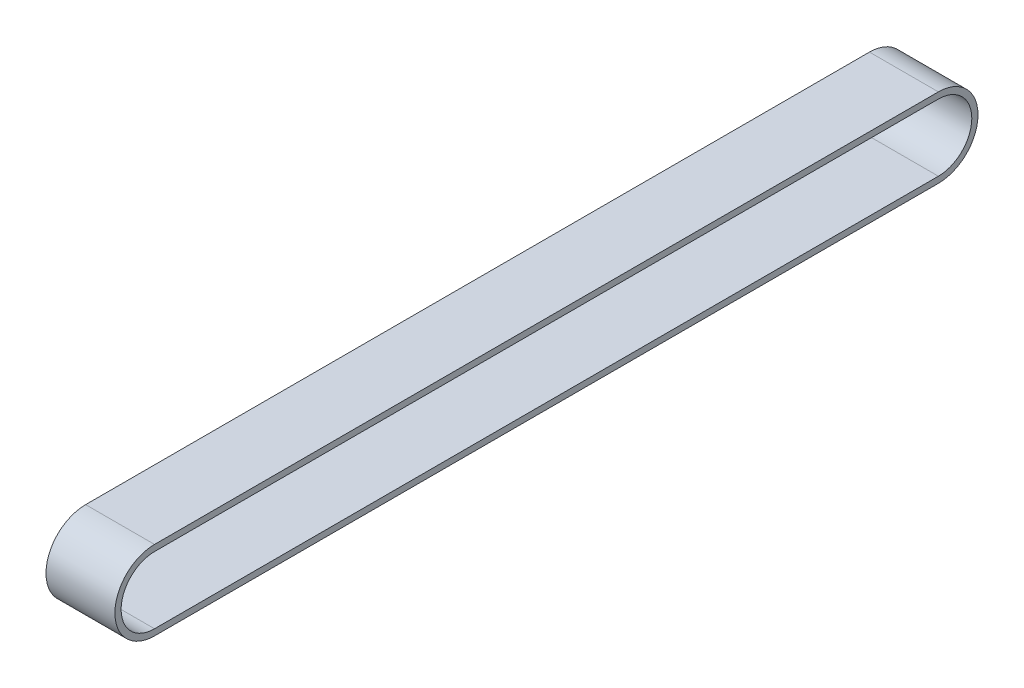
SolidWorks part; units mm, degrees
material "PUR"
ref_plane "Front" through (0, 0, 0) normal (0, 0, 1) x (1, 0, 0)
ref_plane "Top" through (0, 0, 0) normal (0, 1, 0) x (1, 0, 0)
ref_plane "Right" through (0, 0, 0) normal (1, 0, 0) x (0, 0, -1)
sketch "Sketch1" plane through (0, 0, 0) normal (1, 0, 0) x (0, 0, -1)
  line L0 (-144.4625, 0) -> (144.4625, 0) construction
  line L1 (-144.4625, 14.605) -> (144.4625, 14.605)
  line L2 (-144.4625, -14.605) -> (144.4625, -14.605)
  line L3 (-144.4625, 0) -> (144.4625, 0) construction
  line L4 (-144.4625, 12.319) -> (144.4625, 12.319)
  line L5 (-144.4625, -12.319) -> (144.4625, -12.319)
  arc A0 (-144.4625, 14.605) -> (-144.4625, -14.605) centre (-144.4625, 0) ccw
  arc A1 (144.4625, -14.605) -> (144.4625, 14.605) centre (144.4625, 0) ccw
  arc A2 (-144.4625, 12.319) -> (-144.4625, -12.319) centre (-144.4625, 0) ccw
  arc A3 (144.4625, -12.319) -> (144.4625, 12.319) centre (144.4625, 0) ccw
  point P2 (0, 0)
  point P9 (0, 0)
  dimension "D2" = 24.638
  dimension "D1" = 2.286
  dimension "D3" = 288.925
extrude "Boss-Extrude1" add sketch "Sketch1" along normal mid plane 25.4
